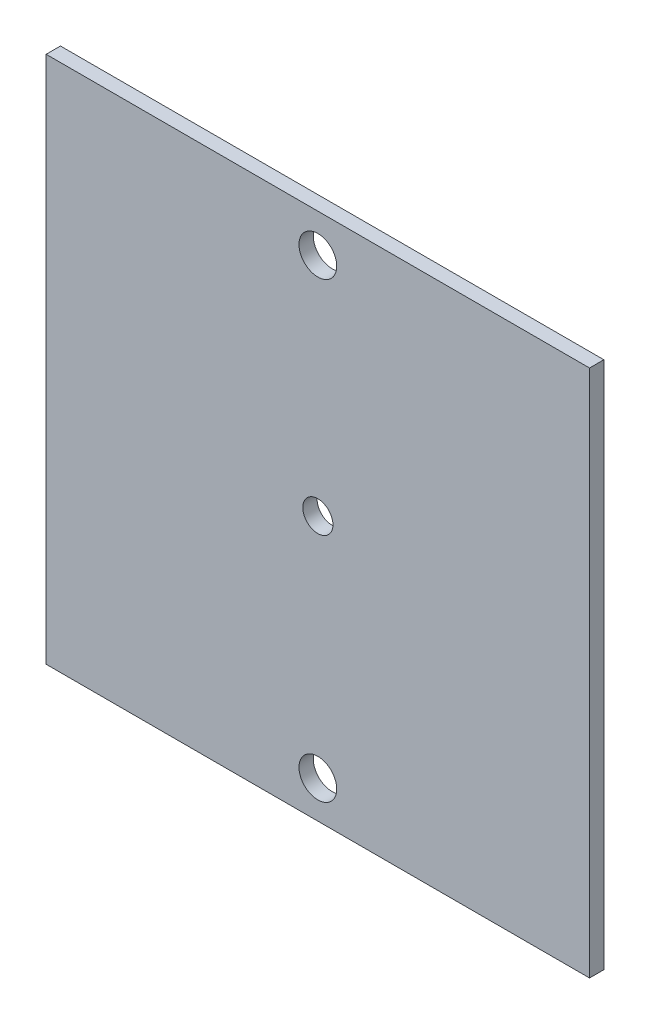
SolidWorks part; units mm, degrees
ref_plane "Front Plane" through (0, 0, 0) normal (0, 0, 1) x (1, 0, 0)
ref_plane "Top Plane" through (0, 0, 0) normal (0, 1, 0) x (1, 0, 0)
ref_plane "Right Plane" through (0, 0, 0) normal (1, 0, 0) x (0, 0, -1)
sketch "Sketch1" plane through (0, 0, 0) normal (0, 0, 1) x (1, 0, 0)
  line L1 (-33.6477, 65.6912) -> (38.3523, 65.6912)
  line L2 (-33.6477, 65.6912) -> (-33.6477, -4.3088)
  line L3 (-33.6477, -4.3088) -> (38.3523, -4.3088)
  line L4 (38.3523, 65.6912) -> (38.3523, -4.3088)
  dimension "D1" = 72
  dimension "D2" = 70
base flange "Base-Flange1" sketch "Sketch1" thickness 1.8974 reverse thickness direction no parameters "D1"=2.54
sketch "Sketch6" plane through (0, 0, 0) normal (0, 0, 1) x (1, 0, 0)
  line L0 (38.3523, -4.3088) -> (38.3523, 65.6912) construction
  circle A0 centre (2.3546, 60.6269) radius 2.5
  circle A1 centre (2.3546, 0.6269) radius 2.5
  circle A2 centre (2.3546, 30.6912) radius 2
  point P6 (38.3523, 30.6912)
  dimension "D1" = 5
extrude "Cut-Extrude1" cut sketch "Sketch6" against normal blind 2 normal cut yes
sketch "Bend-Lines1" plane through (0, 0, 0) normal (0, 1, 0) x (1, 0, 0)
sketch "Bounding-Box1" plane through (0, 0, 0) normal (0, 1, 0) x (1, 0, 0)
sheet metal parameters "Sheet-Metal1" thickness 1.8974 parameters "D1"=2.54
flat pattern "Flat-Pattern1" [suppressed]
sketch "Bend-Lines2" plane through (0, 0, 0) normal (0, 1, 0) x (1, 0, 0)
sketch "Bounding-Box2" [suppressed] plane through (0, 0, 0) normal (0, 1, 0) x (1, 0, 0)
sheet metal parameters "Sheet-Metal2" thickness 1.8974 parameters "D1"=2.54
flat pattern "Flat-Pattern1"
sketch "Bend-Lines2" plane through (0, 0, 0) normal (0, 1, 0) x (1, 0, 0)
sketch "Bounding-Box2" [suppressed] plane through (0, 0, 0) normal (0, 1, 0) x (1, 0, 0)
